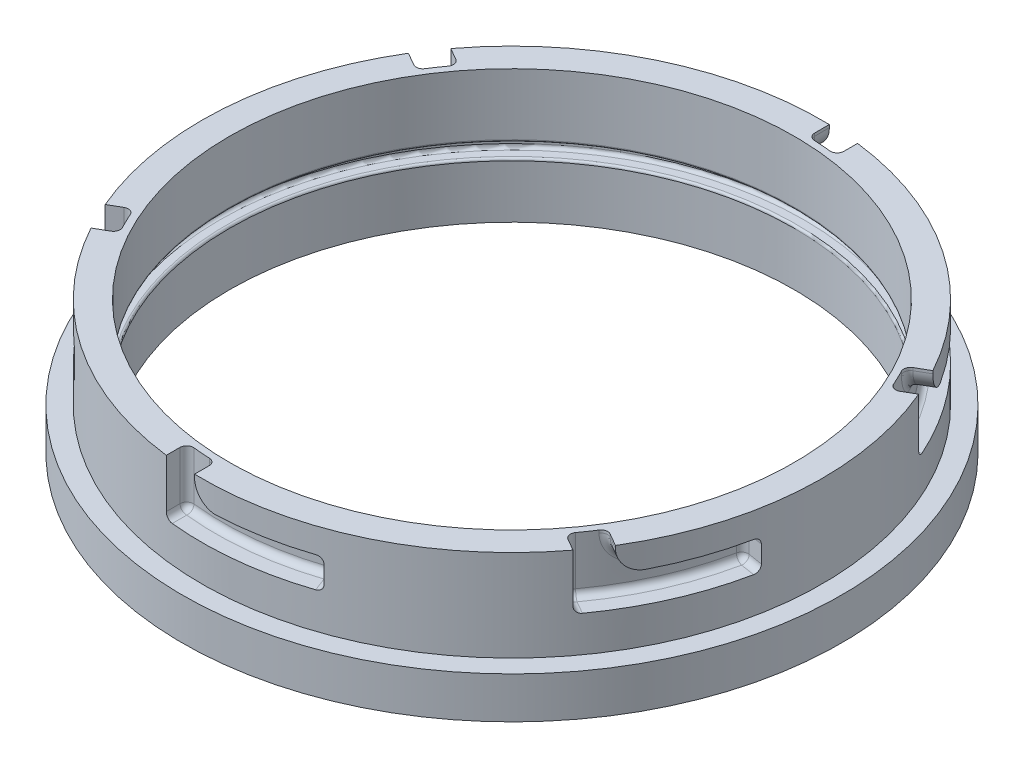
SolidWorks part; units mm, degrees
material "6061-T6 (SS)"
ref_plane "Front Plane" through (0, 0, 0) normal (0, 0, 1) x (1, 0, 0)
ref_plane "Top Plane" through (0, 0, 0) normal (0, 1, 0) x (1, 0, 0)
ref_plane "Right Plane" through (0, 0, 0) normal (1, 0, 0) x (0, 0, -1)
sketch "Sketch1" plane through (0, 0, 0) normal (0, 0, 1) x (1, 0, 0)
  line L0 (0, 60.758) -> (0, -61.3352) construction
  line L1 (71.12, 36.5125) -> (71.12, 15.5575)
  line L2 (71.12, 15.5575) -> (75.565, 15.5575)
  line L3 (75.565, 15.5575) -> (75.565, 6.0325)
  line L4 (75.565, 6.0325) -> (64.77, 6.0325)
  line L5 (64.77, 6.0325) -> (64.77, 18.7325)
  line L6 (64.77, 36.5125) -> (71.12, 36.5125)
  line L7 (64.77, 18.7325) -> (67.818, 18.7325)
  line L8 (67.818, 18.7325) -> (67.818, 21.9075)
  line L9 (67.818, 21.9075) -> (64.77, 21.9075)
  line L10 (64.77, 21.9075) -> (64.77, 36.5125)
  dimension "D1" = 6.35
  dimension "D2" = 9.525
  dimension "D3" = 30.48
  dimension "D4" = 71.12
  dimension "D5" = 75.565
  dimension "D6" = 3.048
  dimension "D7" = 12.7
  dimension "D8" = 15.875
revolve "Revolve1" add sketch "Sketch1" angle 360 about L0
sketch "Sketch2" plane through (0, 36.5125, 0) normal (0, 1, 0) x (1, 0, 0)
  line L0 (-8.6592, -70.5909) -> (-8.6592, -65.726)
  line L1 (-1.6742, -71.1003) -> (-1.6742, -66.2729)
  arc A0 (-1.6742, -71.1003) -> (-8.6592, -70.5909) centre (0, 0) cw
  circle A1 centre (0, 0) radius 71.12 construction
  arc A2 (-1.6742, -66.2729) -> (-8.6592, -65.726) centre (0, 0) cw
  dimension "D1" = 4.826
  dimension "D2" = 6.985
  dimension "D3" = 6.985
extrude "Cut-Extrude1" cut sketch "Sketch2" against normal blind 12.7
sketch "Sketch10" plane through (-1.6742, 0, 0) normal (-1, 0, 0) x (0, 0, 1)
  line L0 (66.2729, 23.8125) -> (66.2729, 30.7975)
  line L1 (66.2729, 23.8125) -> (66.2729, 36.5125) construction
  line L2 (66.2729, 30.7975) -> (71.1003, 30.7975)
  line L3 (71.1003, 23.8125) -> (71.1003, 36.5125) construction
  line L4 (71.1003, 30.7975) -> (71.1003, 23.8125)
  line L5 (71.1003, 23.8125) -> (66.2729, 23.8125)
  dimension "D1" = 6.985
ref_axis "Axis1" through (0, 6.0325, 0) along (0, 1, 0)
sketch "Sketch21" plane through (0, 23.8125, 0) normal (0, 1, 0) x (1, 0, 0)
  line L0 (-1.6742, -71.1003) -> (-1.6742, -66.2729) construction
  arc A0 (-1.6742, -73.5126) -> (73.4476, -3.5158) centre (0, 0) ccw
sketch "Sketch22" plane through (0, 23.8125, 0) normal (0, 1, 0) x (1, 0, 0)
  circle A1 centre (0, 0) radius 73.5317
sketch "Sketch23" plane through (0, 23.8125, 0) normal (0, 1, 0) x (1, 0, 0)
  arc A0 (-1.6742, -71.1003) -> (23.922, -66.9761) centre (0, 0) ccw
sweep "Cut-Sweep2" cut profiles "Sketch10" path "Sketch23"
fillet "Fillet1" radius 5.08 1 edges at (-1.6742, 30.7975, 68.6866)
fillet "Fillet4" radius 1.524 9 edges at (-1.6742, 36.195, 66.2729) (0.2383, 31.9059, 66.2936) (23.0569, 30.7975, 64.7227) (-8.6592, 23.8125, 68.1585) (23.0569, 23.8125, 64.7227) (-8.6592, 30.1625, 65.726) (12.9344, 30.7975, 65.02) (6.9594, 23.8125, 65.9277) (22.1917, 27.305, 62.4694)
pattern_circular "CirPattern1" count 6 over 360 about axis through (0, 60.758, 0) along (0, 1, 0) of "Fillet1", "Cut-Extrude1", "Cut-Sweep2", "Fillet4" reverse direction yes
fillet "Fillet2" radius 0.762 2 edges at (-67.818, 21.9075, 0) (-67.818, 18.7325, 0)
fillet "Fillet3" radius 0.508 2 edges at (-64.77, 18.7325, 0) (-64.77, 21.9075, 0)
sketch "Sketch24" plane through (0, 6.0325, 0) normal (0, -1, 0) x (1, 0, 0)
  line L0 (-2.0961, 67.1054) -> (-1.1566, 67.1033)
  line L1 (-1.6263, 67.1043) -> (-1.6325, 64.2837) construction
  line L2 (-3.1931, 64.513) -> (-0.071, 64.5062)
  spline S0 degree 3 poles (-2.0961, 67.1054) (-2.1672, 66.9295) (-2.2659, 66.6682) (-2.4002, 66.2739) (-2.4676, 66.0573) (-2.5063, 65.9255) knots 0 0 0 0 0.455486 0.670301 1 1 1 1
  spline S1 degree 3 poles (-2.5063, 65.9255) (-2.5773, 65.6449) (-2.6547, 65.2845) (-2.7636, 64.9081) (-2.7851, 64.7854) (-2.8051, 64.7157) (-2.8445, 64.6485) (-2.9065, 64.5845) (-3.0202, 64.5178) (-3.1269, 64.5162) (-3.1931, 64.513) knots 0 0 0 0 0.50758 0.647219 0.68628 0.726157 0.773713 0.821128 0.881401 1 1 1 1
  spline S2 degree 3 poles (-1.1566, 67.1033) (-1.0863, 66.9271) (-0.9887, 66.6654) (-0.8561, 66.2705) (-0.7897, 66.0536) (-0.7516, 65.9217) knots 0 0 0 0 0.455486 0.670301 1 1 1 1
  spline S3 degree 3 poles (-0.7516, 65.9217) (-0.6962, 65.7094) (-0.6454, 65.4407) (-0.5548, 65.1173) (-0.5157, 64.9486) (-0.4854, 64.8115) (-0.4614, 64.7227) (-0.4366, 64.6731) (-0.4076, 64.6316) (-0.3644, 64.5877) (-0.3091, 64.5493) (-0.2095, 64.5089) (-0.1255, 64.5109) (-0.071, 64.5062) knots 0 0 0 0 0.384807 0.478666 0.588978 0.688379 0.725395 0.749588 0.785292 0.813657 0.857185 0.902571 1 1 1 1
